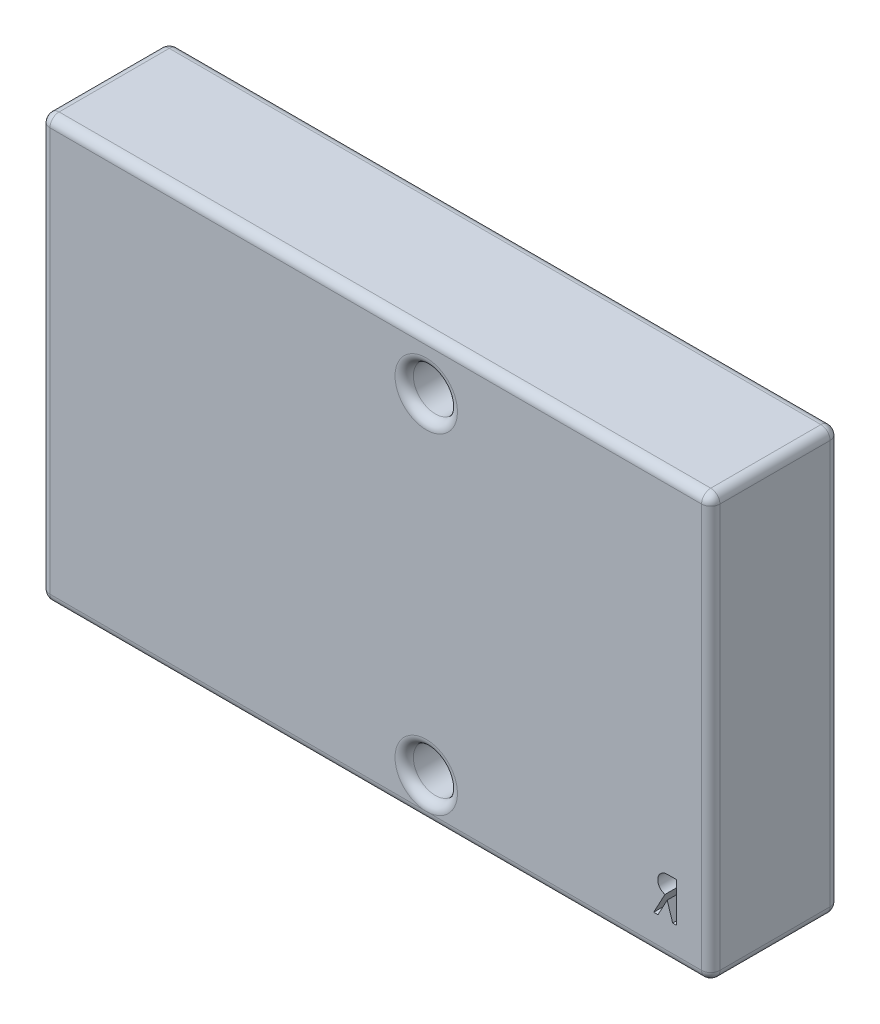
SolidWorks part; units mm, degrees
ref_plane "Front Plane" through (0, 0, 0) normal (0, 0, 1) x (1, 0, 0)
ref_plane "Top Plane" through (0, 0, 0) normal (0, 1, 0) x (1, 0, 0)
ref_plane "Right Plane" through (0, 0, 0) normal (1, 0, 0) x (0, 0, -1)
sketch "Sketch1" plane through (0, 0, 0) normal (0, 1, 0) x (1, 0, 0)
  line L0 (0, 0) -> (36.5, 0)
  line L1 (36.5, 0) -> (36.5, -7)
  line L2 (36.5, -7) -> (0, -7)
  line L3 (0, -7) -> (0, 0)
  dimension "D1" = 36.5
  dimension "D2" = 7
extrude "Boss-Extrude1" add sketch "Sketch1" along normal blind 23
sketch "Sketch2" plane through (0, 0, 0) normal (0, -1, 0) x (1, 0, 0)
  line L0 (36.5, 0) -> (0, 0) construction
  line L1 (36.5, 7) -> (36.5, 0) construction
  line L2 (0, 0) -> (0, 7) construction
  circle A0 centre (8, 3) radius 1.375
  circle A1 centre (28.5, 3) radius 1.375
  dimension "D3" = 2.75
  dimension "D1" = 3
  dimension "D4" = 8
  dimension "D5" = 8
extrude "Cut-Extrude1" cut sketch "Sketch2" against normal blind 8.5
sketch "Sketch4" plane through (0, 0, 0) normal (0, 0, -1) x (-1, 0, 0)
  line L0 (-36.5, 0) -> (0, 0) construction
  line L1 (-28.5, 8.5) -> (-28.5, 0) construction
  circle A0 centre (-21, 2.2) radius 1.2
  circle A1 centre (-21, 20.2) radius 1.2
  dimension "D1" = 2.4
  dimension "D4" = 18
  dimension "D2" = 2.2
  dimension "D3" = 7.5
extrude "Cut-Extrude2" cut sketch "Sketch4" against normal blind 7
fillet "Fillet1" radius 0.5 18 edges at (18.25, 23, 0) (19.8, 20.2, 0) (19.8, 2.2, 0) (0, 11.5, 0) (0, 23, 3.5) (36.5, 23, 3.5) (36.5, 11.5, 0) (0, 11.5, 7) (18.25, 23, 7) (36.5, 11.5, 7) (19.8, 20.2, 7) (19.8, 2.2, 7) (18.25, 0, 7) (36.5, 0, 3.5) (18.25, 0, 0) (0, 0, 3.5) (28.5, 0, 1.625) (8, 0, 1.625)
sketch "Sketch6" plane through (0, 0, 0) normal (0, 0, -1) x (-1, 0, 0)
  line L0 (-34.6263, 1.9429) -> (-34.6263, 4.0985)
  line L1 (-34.6263, 4.0985) -> (-34.1263, 4.0985)
  line L2 (-34.0048, 3.085) -> (-33.3933, 1.94)
  line L3 (-33.3933, 1.94) -> (-33.6263, 1.94)
  line L4 (-33.6263, 1.94) -> (-34.1263, 2.8763)
  line L5 (-34.1263, 2.8763) -> (-34.4263, 1.9429)
  line L6 (-34.4263, 1.9429) -> (-34.6263, 1.9429)
  line L7 (-36, 22.5) -> (-36, 0.5) construction
  line L8 (-36, 0.5) -> (-21, 0.5) construction
  arc A0 (-34.1263, 4.0985) -> (-34.0048, 3.085) centre (-34.1263, 3.5845) cw
  dimension "D5" = 0.514
  dimension "D1" = 0.5
  dimension "D2" = 0.2
  dimension "D3" = 0.233
  dimension "D4" = 2.1555
  dimension "D6" = 0.8
  dimension "D7" = 1.145
  dimension "D8" = 1.3737
  dimension "D9" = 1.4429
  dimension "D10" = 0.5
  dimension "D11" = 1.44
extrude "Cut-Extrude3" cut sketch "Sketch6" against normal through all
